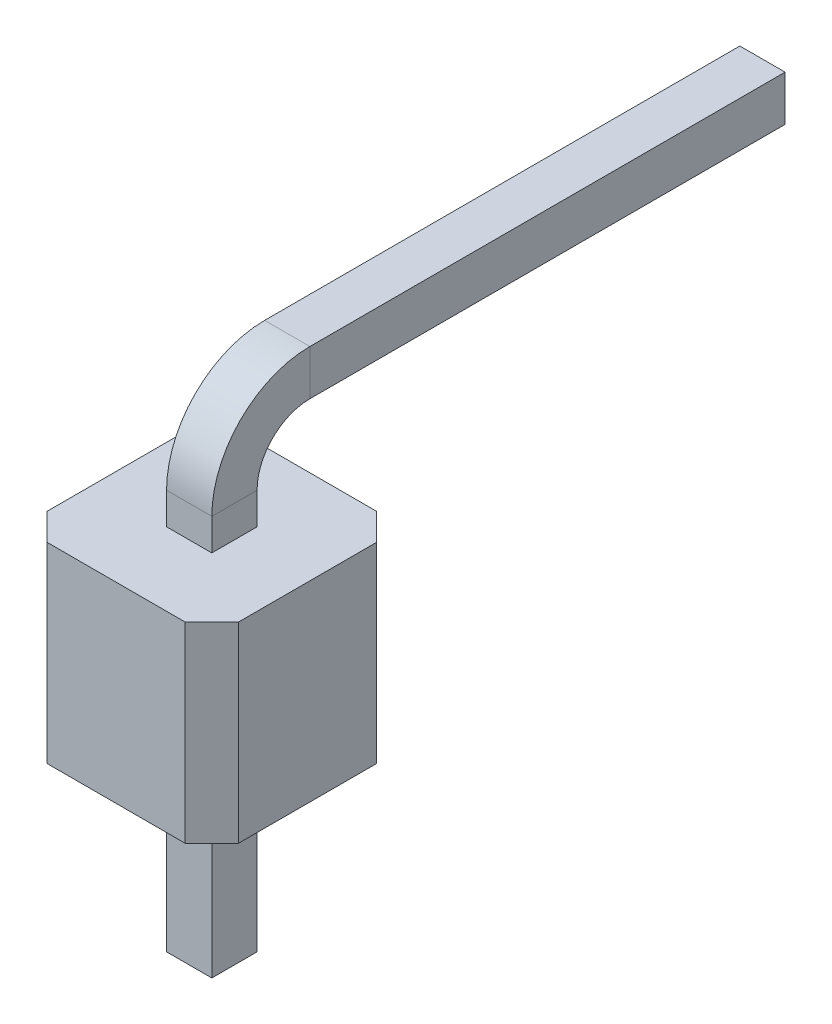
SolidWorks part; units mm, degrees
ref_plane "Alzado" through (0, 0, 0) normal (0, 0, 1) x (1, 0, 0)
ref_plane "Planta" through (0, 0, 0) normal (0, 1, 0) x (1, 0, 0)
ref_plane "Vista lateral" through (0, 0, 0) normal (1, 0, 0) x (0, 0, -1)
sketch "Sketch3" plane through (0, 0, 0) normal (0, 1, 0) x (1, 0, 0)
  line L1 (0.3, -0.3) -> (-0.3, -0.3)
  line L2 (0.3, -0.3) -> (0.3, 0.3)
  line L3 (0.3, 0.3) -> (-0.3, 0.3)
  line L4 (-0.3, -0.3) -> (-0.3, 0.3)
  line L5 (0.3, -0.3) -> (-0.3, 0.3) construction
  line L6 (0.3, 0.3) -> (-0.3, -0.3) construction
  point P0 (0, 0)
  dimension "D1" = 0.6
sketch "Sketch5" plane through (0, 0, 0) normal (1, 0, 0) x (0, 0, -1)
  line L0 (0, 0) -> (0, 5.5)
  line L1 (1, 6.5) -> (7.5, 6.5)
  line L2 (0.3, 0) -> (-0.3, 0) construction
  arc A0 (0, 5.5) -> (1, 6.5) centre (1, 5.5) cw
  point P6 (0, 6.5)
  dimension "D2" = 1
  dimension "D1" = 7.5
  dimension "D3" = 6.5
sweep "Sweep1" add profiles "Sketch3" path "Sketch5"
chamfer "Chamfer3" distance 0.2 angle 45 8 edges at (0, 0, 0.3) (0.3, 0, 0) (0, 0, -0.3) (-0.3, 0, 0) (0, 6.2, -7.5) (0.3, 6.5, -7.5) (0, 6.8, -7.5) (-0.3, 6.5, -7.5)
ref_plane "Plane2" through (0, 2.54, 0) normal (0, 1, 0) x (1, 0, 0)
sketch "Sketch2" plane through (0, 2.54, 0) normal (0, 1, 0) x (1, 0, 0)
  line L0 (-0.9164, 1.27) -> (-1.27, 0.9164)
  line L1 (0.9164, -1.27) -> (-0.9164, -1.27)
  line L2 (1.27, -0.9164) -> (1.27, 0.9164)
  line L3 (0.9164, 1.27) -> (-0.9164, 1.27)
  line L4 (-1.27, -0.9164) -> (-1.27, 0.9164)
  line L5 (0, 1.27) -> (0, -1.27) construction
  line L7 (1.27, 0.9164) -> (0.9164, 1.27)
  line L8 (1.27, -0.9164) -> (0.9164, -1.27)
  line L9 (-0.9164, -1.27) -> (-1.27, -0.9164)
  line L10 (-1.27, 0) -> (1.27, 0) construction
  point P0 (0, 0)
  dimension "D1" = 2.54
  dimension "D2" = 0.5
extrude "Boss-Extrude4" add sketch "Sketch2" along normal blind 2.54
ref_axis "Axis1" through (0, 2.8878, 0) along (0, -1, 0)
